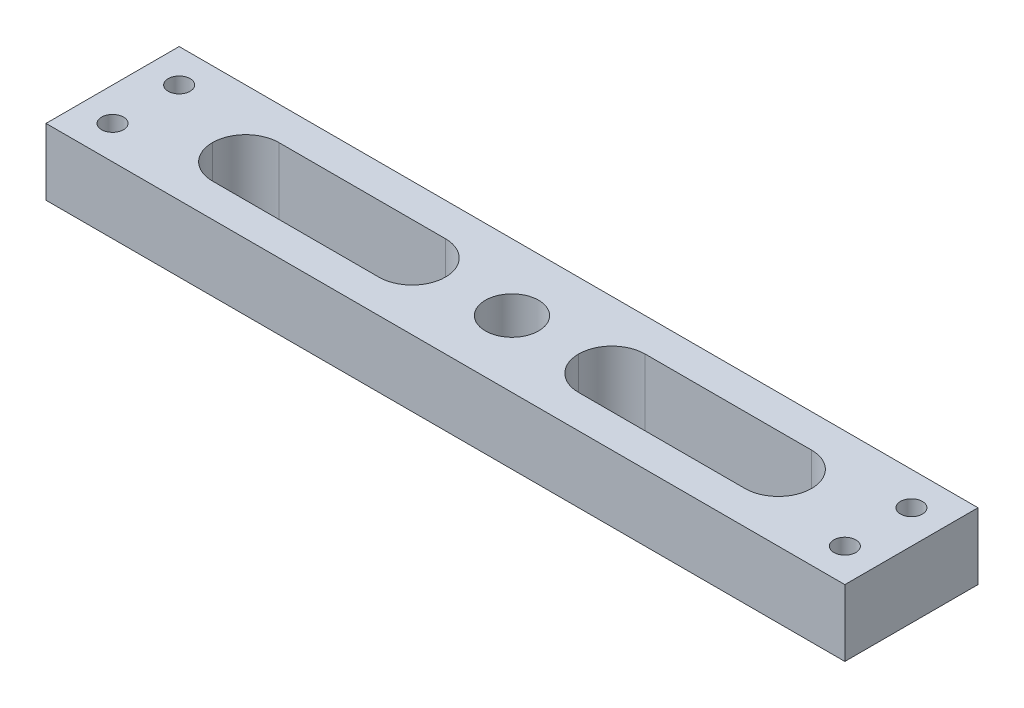
SolidWorks part; units mm, degrees
material "6063-T83"
ref_plane "Front Plane" through (0, 0, 0) normal (0, 0, 1) x (1, 0, 0)
ref_plane "Top Plane" through (0, 0, 0) normal (0, 1, 0) x (1, 0, 0)
ref_plane "Right Plane" through (0, 0, 0) normal (1, 0, 0) x (0, 0, -1)
sketch "Sketch1" plane through (0, 0, 0) normal (0, 1, 0) x (1, 0, 0)
  line L0 (-110, 0) -> (-10, -20) construction
  line L1 (0, 0) -> (-120, 0)
  line L2 (0, 0) -> (0, -20)
  line L3 (0, -20) -> (-120, -20)
  line L4 (-120, 0) -> (-120, -20)
  line L7 (-120, 0) -> (-120, -20) construction
  line L8 (0, -20) -> (-10, -20) construction
  line L9 (-110, 3.4315) -> (-110, -20) construction
  line L10 (-105, -5) -> (-70, -5)
  line L11 (-105, -5) -> (-105, -15)
  line L12 (-105, -15) -> (-70, -15)
  line L13 (-70, -5) -> (-70, -15)
  line L14 (-15, -5) -> (-50, -5)
  line L15 (-15, -5) -> (-15, -15)
  line L16 (-15, -15) -> (-50, -15)
  line L17 (-50, -5) -> (-50, -15)
  line L18 (-10, 3.4315) -> (-10, -20) construction
  circle A0 centre (-60, -10) radius 4
  dimension "D3" = 8
  dimension "D6" = 10
  dimension "D1" = 5
  dimension "D2" = 5
  dimension "D4" = 5
  dimension "D5" = 5
  dimension "D7" = 10
extrude "Boss-Extrude1" add sketch "Sketch1" along normal blind 10
fillet "Fillet1" radius 5 8 edges at (-15, 5, 15) (-15, 5, 5) (-50, 5, 15) (-50, 5, 5) (-105, 5, 5) (-105, 5, 15) (-70, 5, 5) (-70, 5, 15)
hole_wizard "M4x0.7 Tapped Hole1" positions "Sketch2" profile "Sketch3" tap size "M4x0.7" standard "ANSI Metric" end condition through all
sketch "Sketch2" plane through (0, 10, 0) normal (0, 1, 0) x (1, 0, 0)
  line L0 (-115, 0) -> (-115, -5) construction
  line L1 (0, 0) -> (-120, 0) construction
  line L2 (-115, -5) -> (-120, -5) construction
  line L3 (-120, 0) -> (-120, -20) construction
  line L5 (-120, -15) -> (-115, -15) construction
  line L6 (-115, -15) -> (-115, -20) construction
  line L7 (-120, -20) -> (0, -20) construction
  line L10 (-5, -20) -> (-5, -15) construction
  line L11 (-5, -15) -> (0, -15) construction
  line L12 (0, -20) -> (0, 0) construction
  line L15 (0, -5) -> (-5, -5) construction
  line L16 (-5, -5) -> (-5, 0) construction
  point P0 (-115, -5)
  point P2 (-115, -15)
  point P4 (-5, -5)
  point P6 (-5, -15)
  dimension "D1" = 5
sketch "Sketch3" plane through (-115, 10, 5) normal (1, 0, 0) x (0, 0, 1)
  line L0 (0, 0) -> (0, 10)
  line L1 (0, 10) -> (1.65, 10)
  line L2 (1.65, 10) -> (1.65, 0)
  line L5 (1.65, 0) -> (0, 0)
  line L11 (0, -6.35) -> (0, 107.95) construction
  dimension "Thru Tap Drill Dia." = 3.3
  dimension "Thru Tap Drill Depth" = 10
cosmetic thread "Hole Thread1" parameters "D2"=4
cosmetic thread "Hole Thread2" parameters "D2"=4
cosmetic thread "Hole Thread3" parameters "D2"=4
cosmetic thread "Hole Thread4" parameters "D2"=4
